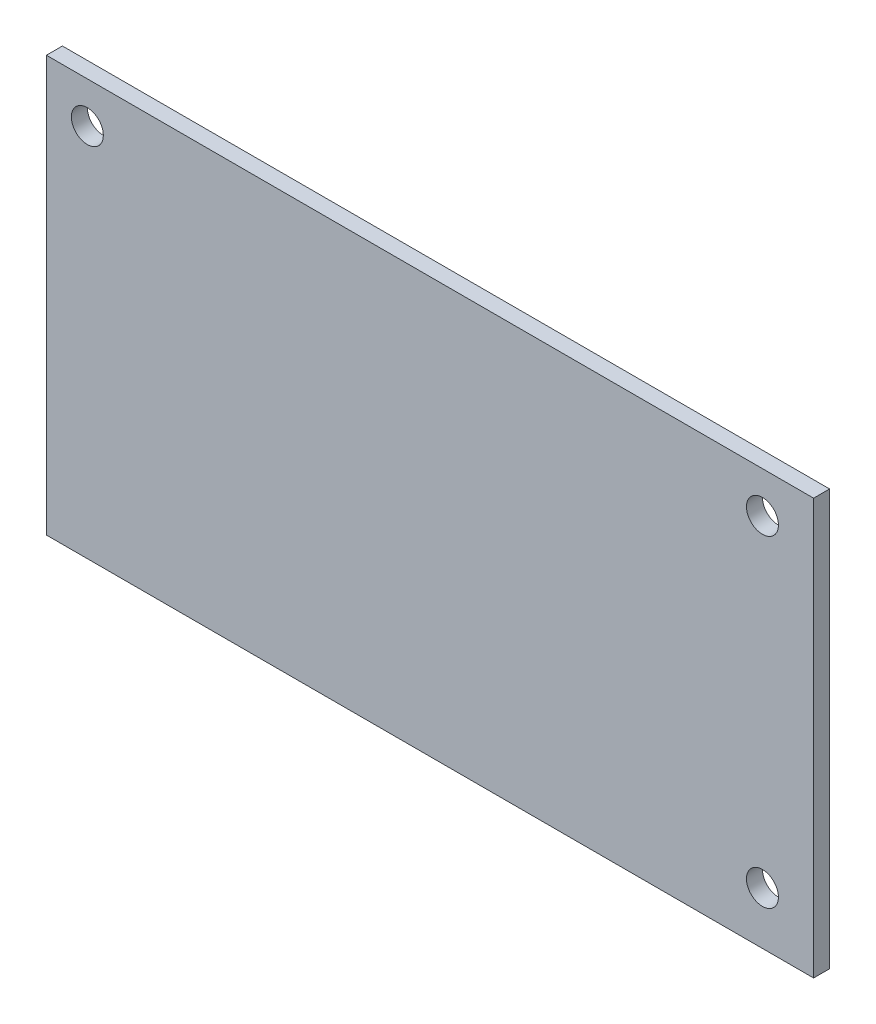
SolidWorks part; units mm, degrees
ref_plane "Front Plane" through (0, 0, 0) normal (0, 0, 1) x (1, 0, 0)
ref_plane "Top Plane" through (0, 0, 0) normal (0, 1, 0) x (1, 0, 0)
ref_plane "Right Plane" through (0, 0, 0) normal (1, 0, 0) x (0, 0, -1)
sketch "Sketch1" plane through (0, 0, 0) normal (0, 0, 1) x (1, 0, 0)
  line L0 (0, 0) -> (76.2, 0)
  line L1 (0, 0) -> (0, 41.275)
  line L2 (76.2, 0) -> (76.2, 41.275)
  line L3 (0, 41.275) -> (76.2, 41.275)
  circle A0 centre (4.064, 37.211) radius 1.5875
  circle A1 centre (71.12, 37.211) radius 1.5875
  circle A2 centre (71.12, 5.207) radius 1.5875
  dimension "D3" = 4.064
  dimension "D7" = 3.175
  dimension "D1" = 76.2
  dimension "D2" = 41.275
  dimension "D4" = 4.064
  dimension "D5" = 67.056
  dimension "D6" = 32.004
extrude "Boss-Extrude1" add sketch "Sketch1" along normal blind 1.5875
sketch "Sketch2" plane through (0, 0, 1.5875) normal (0, 0, 1) x (1, 0, 0)
  line L0 (30.48, 36.195) -> (40.64, 36.195)
  line L1 (30.48, 36.195) -> (30.48, 38.735)
  line L2 (40.64, 36.195) -> (40.64, 38.735)
  line L3 (30.48, 38.735) -> (40.64, 38.735)
  line L4 (43.18, 36.195) -> (50.8, 36.195)
  line L5 (43.18, 36.195) -> (43.18, 38.735)
  line L6 (50.8, 36.195) -> (50.8, 38.735)
  line L7 (43.18, 38.735) -> (50.8, 38.735)
  line L8 (0, 41.275) -> (0, 0) construction
  line L9 (3.175, 19.05) -> (6.35, 19.05)
  line L10 (3.175, 19.05) -> (3.175, 15.875)
  line L11 (3.175, 15.875) -> (6.35, 15.875)
  line L12 (6.35, 19.05) -> (6.35, 15.875)
  line L13 (6.35, 15.875) -> (3.175, 15.875)
  line L14 (6.35, 15.875) -> (6.35, 12.7)
  line L15 (6.35, 12.7) -> (3.175, 12.7)
  line L16 (3.175, 15.875) -> (3.175, 12.7)
  line L17 (3.175, 12.7) -> (6.35, 12.7)
  line L18 (3.175, 12.7) -> (3.175, 9.525)
  line L19 (3.175, 9.525) -> (6.35, 9.525)
  line L20 (6.35, 12.7) -> (6.35, 9.525)
  line L21 (6.35, 9.525) -> (3.175, 9.525)
  line L22 (6.35, 9.525) -> (6.35, 6.35)
  line L23 (6.35, 6.35) -> (3.175, 6.35)
  line L24 (3.175, 9.525) -> (3.175, 6.35)
  line L25 (0, 0) -> (76.2, 0) construction
  line L26 (76.2, 0) -> (76.2, 41.275) construction
  line L27 (76.2, 41.275) -> (0, 41.275) construction
  point P27 (38.1, 41.275)
  dimension "D1" = 3.175
  dimension "D2" = 6.35
  dimension "D3" = 3.175
  dimension "D4" = 10.16
  dimension "D5" = 7.62
  dimension "D6" = 2.54
  dimension "D7" = 25.4
  dimension "D8" = 2.54
  dimension "D9" = 2.54
